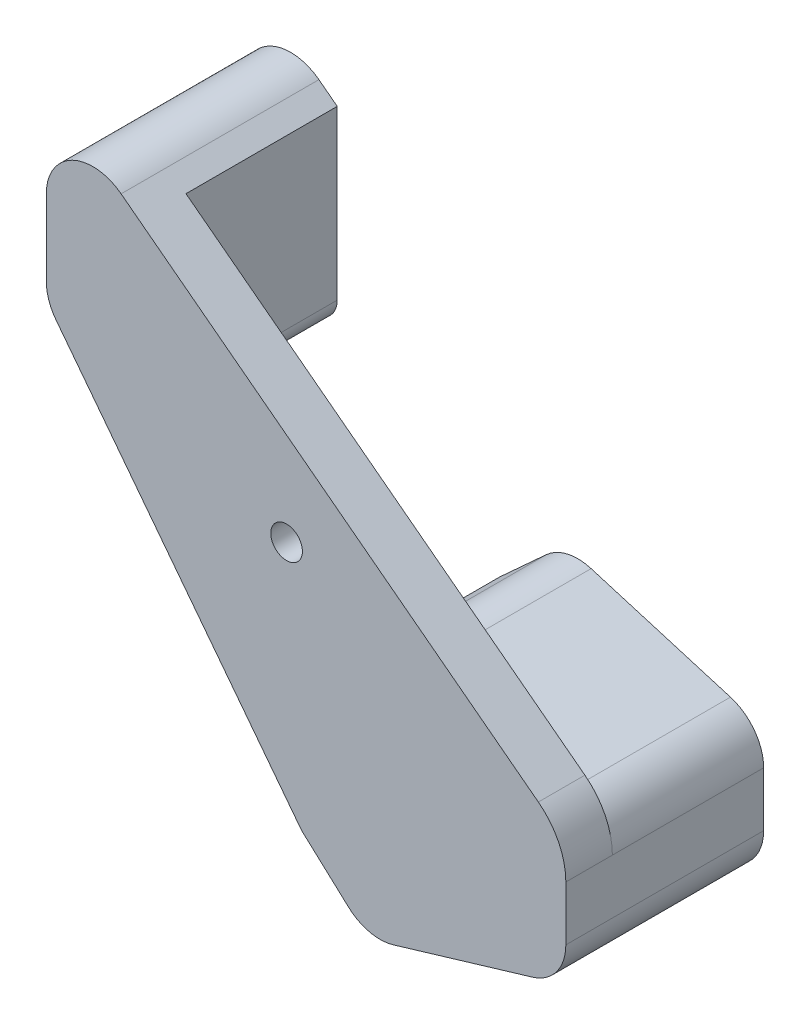
SolidWorks part; units mm, degrees
ref_plane "Front Plane" through (0, 0, 0) normal (0, 0, 1) x (1, 0, 0)
ref_plane "Top Plane" through (0, 0, 0) normal (0, 1, 0) x (1, 0, 0)
ref_plane "Right Plane" through (0, 0, 0) normal (1, 0, 0) x (0, 0, -1)
sketch "Sketch1" plane through (0, 0, 0) normal (0, 0, 1) x (1, 0, 0)
  line L0 (0, 0) -> (0, 12.7)
  line L1 (0, 12.7) -> (11.1125, 22.86)
  line L3 (11.1125, 22.86) -> (38.1, 14.7942)
  line L4 (38.1, 14.7942) -> (38.1, -19.05)
  line L5 (11.1125, 12.7) -> (11.1125, 0) construction
  line L6 (11.1125, 6.35) -> (30.1625, 6.35) construction
  line L7 (11.1125, -10.16) -> (38.1, -2.0942)
  line L8 (0, 0) -> (11.1125, -10.16)
  circle A0 centre (11.1125, 12.7) radius 2.032
  circle A1 centre (11.1125, 0) radius 2.032
  circle A2 centre (30.1625, 6.35) radius 2.032
  dimension "D3" = 4.064
  dimension "D1" = 73.36
  dimension "D2" = 38.1
  dimension "D4" = 11.1125
  dimension "D5" = 12.7
  dimension "D6" = 10.16
  dimension "D7" = 19.05
  dimension "D8" = 19.05
extrude "Boss-Extrude1" add sketch "Sketch1" along normal blind 20.6375 contours L0 L8 L7 L4 L3 L1 A2 A1 A0 region at (18.6064, 6.35, 0)
fillet "Fillet1" radius 6.35 6 edges at (38.1, 14.7942, 10.3187) (11.1125, 22.86, 10.3187) (0, 12.7, 10.3187) (38.1, -2.0942, 10.3187) (11.1125, -10.16, 10.3187) (0, 0, 10.3187)
sketch "Sketch3" plane through (0, 0, 20.6375) normal (0, 0, 1) x (1, 0, 0)
  line L0 (2.0652, -1.8882) -> (-32.7759, 43.4132)
  line L1 (-32.7759, 43.4132) -> (-32.7759, 68.8132)
  line L2 (-32.7759, 68.8132) -> (34.3497, 17.6393)
  line L6 (14.5601, -9.1296) -> (33.5684, -3.4485)
  line L7 (38.1, 2.6355) -> (38.1, 10.0645)
  line L8 (33.5684, 16.1485) -> (14.5601, 21.8296)
  line L9 (8.4569, 20.432) -> (2.0652, 14.5882)
  line L10 (0, 9.9017) -> (0, 2.7983)
  line L11 (2.0652, -1.8882) -> (8.4569, -7.732)
  line L12 (14.5601, -9.1296) -> (33.5684, -3.4485)
  line L13 (38.1, 2.6355) -> (38.1, 10.0645)
  line L17 (2.0652, -1.8882) -> (8.4569, -7.732)
  arc A0 (38.1, 10.0645) -> (34.3497, 17.6393) centre (28.575, 10.0645) ccw
  circle A1 centre (0, 31.1519) radius 2.159 construction
  circle A2 centre (0, 31.1519) radius 2.159
  arc A6 (33.5684, -3.4485) -> (38.1, 2.6355) centre (31.75, 2.6355) ccw
  arc A7 (38.1, 10.0645) -> (33.5684, 16.1485) centre (31.75, 10.0645) ccw
  arc A8 (14.5601, 21.8296) -> (8.4569, 20.432) centre (12.7417, 15.7455) ccw
  arc A9 (2.0652, 14.5882) -> (0, 9.9017) centre (6.35, 9.9017) ccw
  arc A10 (0, 2.7983) -> (2.0652, -1.8882) centre (6.35, 2.7983) ccw
  arc A11 (8.4569, -7.732) -> (14.5601, -9.1296) centre (12.7417, -3.0455) ccw
  arc A12 (33.5684, -3.4485) -> (38.1, 2.6355) centre (31.75, 2.6355) ccw
  arc A17 (8.4569, -7.732) -> (14.5601, -9.1296) centre (12.7417, -3.0455) ccw
  dimension "D2" = 57.15
  dimension "D3" = 9.525
  dimension "D4" = 170
  dimension "D5" = 25.4
  dimension "D1" = 0
extrude "Boss-Extrude2" add sketch "Sketch3" along normal blind 6.35
fillet "Fillet2" radius 6.35 2 edges at (-32.7759, 43.4132, 23.8125) (-32.7759, 68.8132, 23.8125)
sketch "Sketch4" plane through (0, 0, 20.6375) normal (0, 0, -1) x (-1, 0, 0)
  line L0 (32.7759, 55.9874) -> (32.7759, 45.5727) construction
  line L1 (32.7759, 55.9874) -> (32.7759, 45.5727)
  line L2 (22.5761, 61.0373) -> (20.0759, 59.1312)
  line L3 (-34.3497, 17.6393) -> (22.5761, 61.0373) construction
  line L4 (31.4594, 41.7014) -> (20.0759, 26.9003)
  line L5 (20.0759, 59.1312) -> (20.0759, 26.9003)
  arc A0 (31.4594, 41.7014) -> (32.7759, 45.5727) centre (26.4259, 45.5727) ccw construction
  arc A1 (32.7759, 55.9874) -> (22.5761, 61.0373) centre (26.4259, 55.9874) ccw construction
  arc A2 (31.4594, 41.7014) -> (32.7759, 45.5727) centre (26.4259, 45.5727) ccw
  arc A3 (32.7759, 55.9874) -> (22.5761, 61.0373) centre (26.4259, 55.9874) ccw
  circle A4 centre (26.4259, 55.9874) radius 2.032
  circle A5 centre (26.4259, 45.5727) radius 2.032
  dimension "D2" = 4.064
  dimension "D1" = 12.7
extrude "Boss-Extrude3" add sketch "Sketch4" along normal up to surface (20.6375 mm away)
ref_plane "Plane1" through (0, 0, -2.54) normal (0, 0, -1) x (-1, 0, 0)
fillet "Fillet3" radius 3.175 1 edges at (-20.0759, 26.9003, 10.3188)
mirror "Mirror2" [suppressed] about plane through (0, 0, -2.54) normal (0, 0, -1) of bodies 103
delete or keep bodies "Body-Delete/Keep 1" [suppressed] type delete bodies bodies 103
